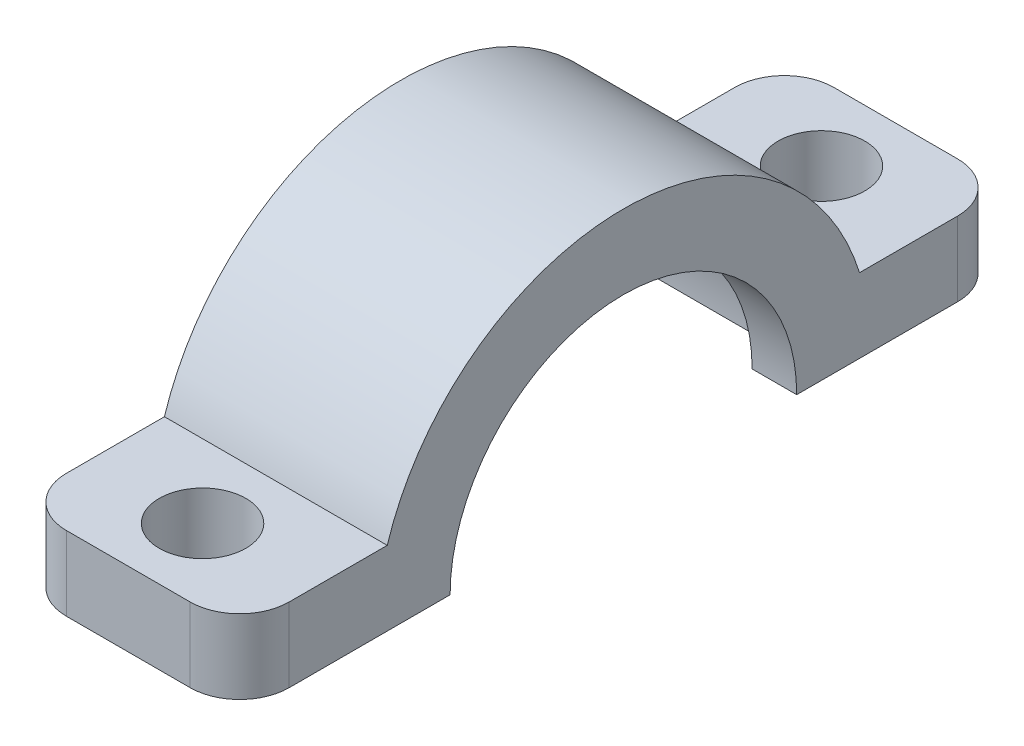
SolidWorks part; units mm, degrees
ref_plane "Front Plane" through (0, 0, 0) normal (0, 0, 1) x (1, 0, 0)
ref_plane "Top Plane" through (0, 0, 0) normal (0, 1, 0) x (1, 0, 0)
ref_plane "Right Plane" through (0, 0, 0) normal (1, 0, 0) x (0, 0, -1)
sketch "Sketch2" plane through (0, 0, 0) normal (1, 0, 0) x (0, 0, -1)
  line L0 (9.5394, 1.5) -> (15.5, 1.5)
  line L1 (-15.5, 1.5) -> (-9.5394, 1.5)
  line L2 (-15.5, 1.5) -> (-15.5, -1.5)
  line L3 (-15.5, -1.5) -> (-7, -1.5)
  line L4 (15.5, 1.5) -> (15.5, -1.5)
  line L5 (-6.6633, 0.6448) -> (15.5, -1.5) construction
  line L6 (-15.5, -1.5) -> (15.5, 1.5) construction
  line L7 (7, -1.5) -> (15.5, -1.5)
  arc A0 (9.5394, 1.5) -> (-9.5394, 1.5) centre (0, -1.5) ccw
  arc A1 (7, -1.5) -> (-7, -1.5) centre (0, -1.5) ccw
  point P0 (0, 0)
  dimension "D3" = 10
  dimension "D4" = 7
  dimension "D1" = 31
  dimension "D2" = 3
extrude "Boss-Extrude1" add sketch "Sketch2" along normal blind 4.5 and the other way blind 4.5
sketch "Sketch3" plane through (0, 1.5, 0) normal (0, 1, 0) x (1, 0, 0)
  line L0 (0, 12.5) -> (0, 0) construction
  line L1 (0, 0) -> (0, -12.5) construction
  line L2 (-4.5, -15.5) -> (4.5, -15.5) construction
  line L3 (-4.5, 15.5) -> (4.5, 15.5) construction
  circle A0 centre (0, 12.5) radius 1.75
  circle A1 centre (0, -12.5) radius 1.75
  dimension "D3" = 3.5
  dimension "D4" = 3.5
  dimension "D1" = 3
  dimension "D2" = 3
extrude "Cut-Extrude1" cut sketch "Sketch3" against normal through all
fillet "Fillet1" radius 2 4 edges at (4.5, 0, 15.5) (-4.5, 0, 15.5) (4.5, 0, -15.5) (-4.5, 0, -15.5)
sketch "Sketch4" plane through (0, 0, 0) normal (1, 0, 0) x (0, 0, -1)
  circle A0 centre (0, -1.5) radius 8.25
  dimension "D1" = 16.5
extrude "Cut-Extrude2" cut sketch "Sketch4" against normal blind 2.7 and the other way blind 2.7
